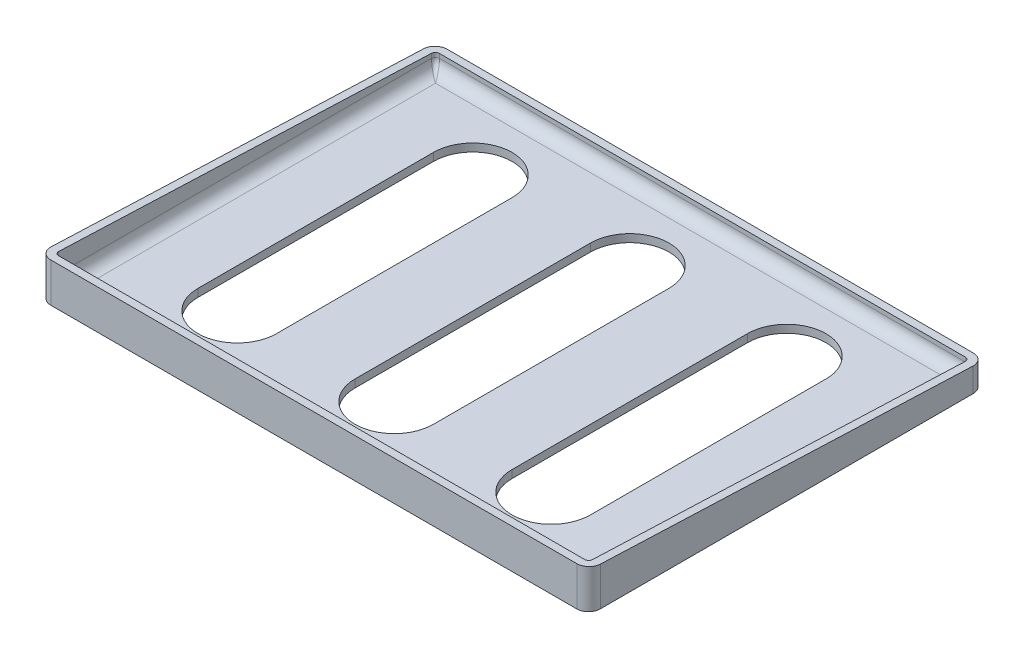
SolidWorks part; units mm, degrees
ref_plane "Front Plane" through (0, 0, 0) normal (0, 0, 1) x (1, 0, 0)
ref_plane "Top Plane" through (0, 0, 0) normal (0, 1, 0) x (1, 0, 0)
ref_plane "Right Plane" through (0, 0, 0) normal (1, 0, 0) x (0, 0, -1)
sketch "Sketch1" plane through (0, 0, 0) normal (1, 0, 0) x (0, 0, -1)
  line L0 (0, 0) -> (0, 10)
  line L1 (0, 10) -> (101, 6)
  line L2 (101, 6) -> (101, 0)
  line L3 (101, 0) -> (0, 0)
  dimension "D1" = 101
  dimension "D2" = 10
  dimension "D3" = 6
extrude "Boss-Extrude1" add sketch "Sketch1" along normal mid plane 140
fillet "Fillet2" radius 3 4 edges at (70, 3, -101) (70, 5, 0) (-70, 5, 0) (-70, 3, -101)
shell "Shell1" thickness 2 removed face at (0, 8, -50.5)
fillet "Fillet1" radius 3 8 edges at (0, 2, -99) (68, 2, -50.5) (0, 2, -2) (-68, 2, -50.5) (67.7071, 2, -98.7071) (67.7071, 2, -2.2929) (-67.7071, 2, -2.2929) (-67.7071, 2, -98.7071)
sketch "Sketch2" plane through (0, 2, 0) normal (0, 1, 0) x (1, 0, 0)
  line L0 (-40, 80.5) -> (-40, 20.5) construction
  line L1 (-30, 80.5) -> (-30, 20.5)
  line L2 (-50, 80.5) -> (-50, 20.5)
  line L3 (-65, 96) -> (-65, 5) construction
  line L4 (-70, 98) -> (-70, 3) construction
  line L5 (0, 80.5) -> (0, 20.5) construction
  line L6 (10, 80.5) -> (10, 20.5)
  line L7 (-10, 80.5) -> (-10, 20.5)
  line L8 (40, 80.5) -> (40, 20.5) construction
  line L9 (50, 80.5) -> (50, 20.5)
  line L10 (30, 80.5) -> (30, 20.5)
  line L11 (70, 98) -> (70, 3) construction
  arc A0 (-30, 80.5) -> (-50, 80.5) centre (-40, 80.5) ccw
  arc A1 (-50, 20.5) -> (-30, 20.5) centre (-40, 20.5) ccw
  arc A2 (10, 80.5) -> (-10, 80.5) centre (0, 80.5) ccw
  arc A3 (-10, 20.5) -> (10, 20.5) centre (0, 20.5) ccw
  arc A4 (50, 80.5) -> (30, 80.5) centre (40, 80.5) ccw
  arc A5 (30, 20.5) -> (50, 20.5) centre (40, 20.5) ccw
  point P2 (-40, 50.5)
  point P9 (-65, 50.5)
  point P14 (0, 50.5)
  point P20 (0, 0)
  point P21 (0, 0)
  point P24 (40, 50.5)
  point P29 (0, 0)
  point P30 (0, 0)
  dimension "D2" = 10
  dimension "D1" = 60
  dimension "D3" = 20
  dimension "D4" = 20
extrude "Cut-Extrude1" cut sketch "Sketch2" against normal through all both and the other way through all
